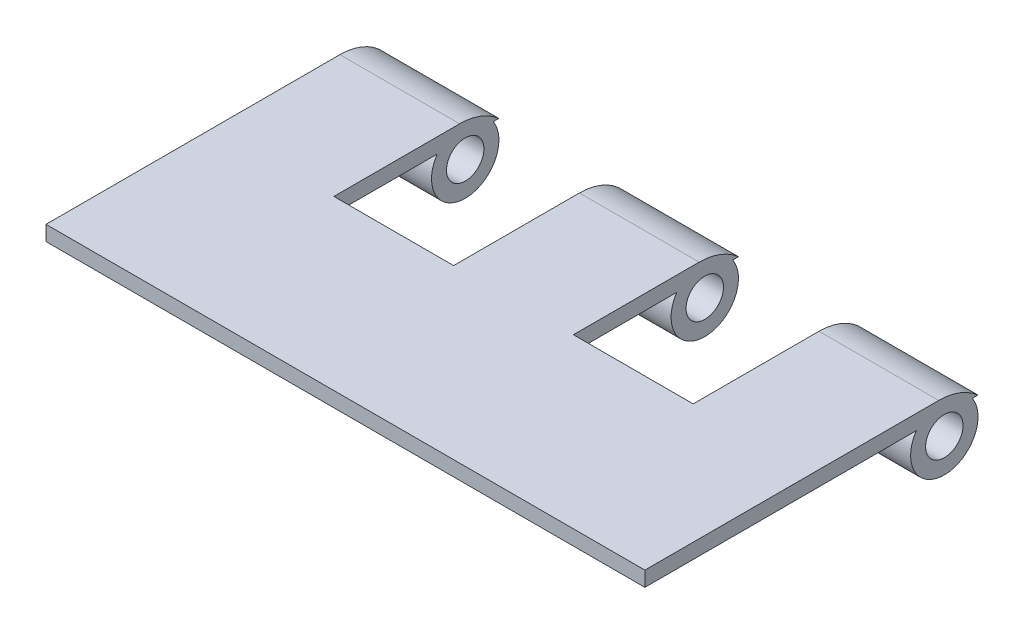
SolidWorks part; units mm, degrees
material "Brass"
ref_plane "Front Plane" through (0, 0, 0) normal (0, 0, 1) x (1, 0, 0)
ref_plane "Top Plane" through (0, 0, 0) normal (0, 1, 0) x (1, 0, 0)
ref_plane "Right Plane" through (0, 0, 0) normal (1, 0, 0) x (0, 0, -1)
sketch "Sketch1" plane through (0, 0, 0) normal (0, 1, 0) x (1, 0, 0)
  line L1 (-11.7699, 14.8926) -> (13.6301, 14.8926)
  line L2 (-11.7699, 14.8926) -> (-11.7699, 0.7639)
  line L3 (-11.7699, 0.7639) -> (13.6301, 0.7639)
  line L4 (13.6301, 14.8926) -> (13.6301, 0.7639)
  line L5 (-6.6899, 14.8926) -> (-1.6099, 14.8926)
  line L6 (-6.6899, 14.8926) -> (-6.6899, 7.8926)
  line L7 (-6.6899, 7.8926) -> (-1.6099, 7.8926)
  line L8 (-1.6099, 14.8926) -> (-1.6099, 7.8926)
  line L9 (3.4701, 14.8926) -> (8.5501, 14.8926)
  line L10 (3.4701, 14.8926) -> (3.4701, 7.8926)
  line L11 (3.4701, 7.8926) -> (8.5501, 7.8926)
  line L12 (8.5501, 14.8926) -> (8.5501, 7.8926)
  dimension "D5" = 5.08
  dimension "D6" = 5.08
  dimension "D1" = 14.1288
  dimension "D2" = 25.4
  dimension "D3" = 5.08
  dimension "D4" = 5.08
  dimension "D13" = 7
  dimension "D14" = 7
extrude "Boss-Extrude1" add sketch "Sketch1" along normal blind 0.635 contours L1 L12 L11 L10 L8 L7 L6 L2 L3 L4 region at (0.9301, 0, -6.9473)
sketch "Sketch2" plane through (13.6301, 0, 0) normal (1, 0, 0) x (0, 0, -1)
  line L1 (14.8926, 0.635) -> (14.8926, 0) construction
  line L3 (14.8926, 0.635) -> (0.7639, 0.635) construction
  circle A0 centre (13.4639, -0.7937) radius 1.4288
  dimension "D2" = 2.8575
  dimension "D3" = 1.4287
  dimension "D1" = 1.4287
extrude "Boss-Extrude2" add sketch "Sketch2" against normal up to surface (25.4 mm away) up to face at (-11.7699, 0.3175, -7.8282)
sketch "Sketch3" plane through (0, 0.635, 0) normal (0, 1, 0) x (1, 0, 0)
  line L0 (8.5501, 13.4639) -> (8.5501, 7.8926) construction
  line L1 (-6.6899, 14.8926) -> (-1.6099, 14.8926)
  line L2 (-6.6899, 14.8926) -> (-6.6899, 7.8926)
  line L3 (-6.6899, 7.8926) -> (-1.6099, 7.8926)
  line L4 (-1.6099, 14.8926) -> (-1.6099, 7.8926)
  line L5 (3.4701, 14.8926) -> (8.5501, 14.8926)
  line L6 (3.4701, 14.8926) -> (3.4701, 7.8926)
  line L7 (3.4701, 7.8926) -> (8.5501, 7.8926)
  line L8 (8.5501, 14.8926) -> (8.5501, 7.8926)
  dimension "D1" = 0
extrude "Cut-Extrude1" cut sketch "Sketch3" against normal blind 40
sketch "Sketch4" plane through (13.6301, 0, 0) normal (1, 0, 0) x (0, 0, -1)
  circle A0 centre (13.4639, -0.7937) radius 0.7937
  dimension "D1" = 1.5875
extrude "Cut-Extrude2" cut sketch "Sketch4" against normal blind 40
fillet "Fillet1" radius 2.5 3 edges at (-9.2299, 0.635, -14.8926) (0.9301, 0.635, -14.8926) (11.0901, 0.635, -14.8926)
